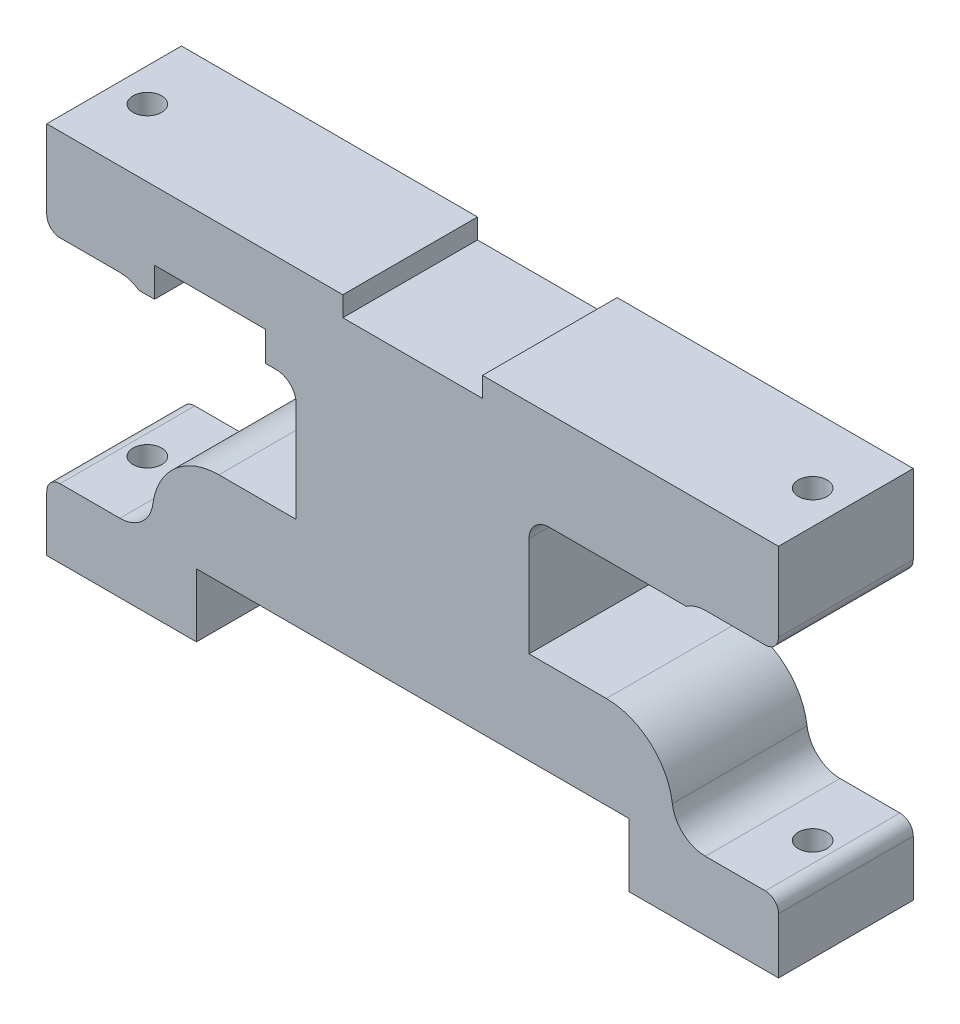
SolidWorks part; units mm, degrees
ref_plane "Front Plane" through (0, 0, 0) normal (0, 0, 1) x (1, 0, 0)
ref_plane "Top Plane" through (0, 0, 0) normal (0, 1, 0) x (1, 0, 0)
ref_plane "Right Plane" through (0, 0, 0) normal (1, 0, 0) x (0, 0, -1)
sketch "Sketch1" plane through (0, 0, 0) normal (0, 1, 0) x (1, 0, 0)
  line L0 (-50, 0) -> (-47.841, 0) construction
  line L21 (47.841, 0) -> (50, 0) construction
  line L22 (-50, 0) -> (-47.841, 0) construction
  line L38 (47.841, 0) -> (50, 0) construction
  line L40 (-55, 10.125) -> (55, 10.125)
  line L41 (-55, 10.125) -> (-55, -10.125)
  line L42 (-55, -10.125) -> (55, -10.125)
  line L43 (55, 10.125) -> (55, -10.125)
  line L44 (-55, 10.125) -> (55, -10.125) construction
  line L45 (-55, -10.125) -> (55, 10.125) construction
  circle A0 centre (-50, 0) radius 2.159
  circle A1 centre (50, 0) radius 2.159
  point P0 (0, 0)
  point P1 (0, 0)
  dimension "D4" = 4.318
  dimension "D5" = 4.318
  dimension "D6" = 5
  dimension "D2" = 20.25
  dimension "D3" = 110
  dimension "D1" = 100
extrude "Boss-Extrude1" add sketch "Sketch1" along normal blind 43.175
sketch "Sketch2" plane through (0, 0, 0) normal (1, 0, 0) x (0, 0, -1)
  line L0 (-10.125, 0) -> (10.125, 0) construction
  line L1 (-36.8851, 36) -> (38.0609, 36)
  line L2 (-36.8851, 36) -> (-36.8851, 4)
  line L3 (-36.8851, 4) -> (38.0609, 4)
  line L4 (38.0609, 36) -> (38.0609, 4)
  dimension "D1" = 32
  dimension "D2" = 4
extrude "Cut-Extrude3" cut sketch "Sketch2" along normal through all from offset 39 contours L4 L3 L2 L1
extrude "Cut-Extrude4" cut sketch "Sketch2<3>" against normal through all from offset 39 offset against normal yes
sketch "Sketch2<3>" plane through (0, 0, 0) normal (1, 0, 0) x (0, 0, -1) same geometry as "Sketch2"
fillet "Fillet1" radius 5 4 edges at (-39, 36, 0) (-39, 4, 0) (39, 4, 0) (39, 36, 0)
fillet "Fillet2" radius 2 4 edges at (55, 4, 0) (55, 36, 0) (-55, 36, 0) (-55, 4, 0)
sketch "Sketch10" plane through (0, 0, 0) normal (0, -1, 0) x (1, 0, 0)
  line L0 (55, -10.125) -> (-55, -10.125) construction
  line L1 (-32.5, 10.125) -> (32.5, 10.125)
  line L2 (-32.5, 10.125) -> (-32.5, -10.125)
  line L3 (-32.5, -10.125) -> (32.5, -10.125)
  line L4 (32.5, 10.125) -> (32.5, -10.125)
  line L5 (-32.5, 10.125) -> (32.5, -10.125) construction
  line L6 (-32.5, -10.125) -> (32.5, 10.125) construction
  point P0 (0, 0)
  dimension "D1" = 65
extrude "Cut-Extrude8" cut sketch "Sketch10" against normal blind 3.175
sketch "Sketch11" plane through (0, 0, 10.125) normal (0, 0, 1) x (1, 0, 0)
  line L0 (17.5, 17.0962) -> (47.5, 17.0962)
  line L1 (-46.8673, 35.0962) -> (-17.5, 35.0962)
  line L2 (-46.8673, 35.0962) -> (-46.8673, 17.0962)
  line L3 (-46.8673, 17.0962) -> (-17.5, 17.0962)
  line L4 (47.5, 35.0962) -> (47.5, 17.0962)
  line L6 (-17.5, 35.0962) -> (-17.5, 17.0962)
  line L8 (17.5, 35.0962) -> (17.5, 17.0962)
  line L11 (17.5, 35.0962) -> (47.5, 35.0962)
  arc A0 (-39, 31) -> (-44, 36) centre (-44, 31) ccw construction
  point P7 (0, 30.7484)
  dimension "D1" = 17.5
  dimension "D2" = 17.5
  dimension "D3" = 18
extrude "Cut-Extrude9" cut sketch "Sketch11" against normal through all
fillet "Fillet3" radius 10 2 edges at (39, 17.0962, 0) (-39, 17.0962, 0)
fillet "Fillet5" radius 3 2 edges at (17.5, 35.0962, 0) (-17.5, 35.0962, 0)
sketch "Sketch13" plane through (0, 43.175, 0) normal (0, 1, 0) x (1, 0, 0)
  line L1 (-55, 10.125) -> (55, 10.125)
  line L2 (-55, 10.125) -> (-55, -10.125)
  line L3 (-55, -10.125) -> (55, -10.125)
  line L4 (55, 10.125) -> (55, -10.125)
sketch "Sketch16" plane through (0, 0, 0) normal (0, -1, 0) x (1, 0, 0)
  line L1 (-55, 10.125) -> (-32.5, 10.125)
  line L2 (-55, 10.125) -> (-55, -10.125)
  line L3 (-55, -10.125) -> (-32.5, -10.125)
  line L4 (-32.5, 10.125) -> (-32.5, -10.125)
  line L5 (32.5, 10.125) -> (55, 10.125)
  line L6 (32.5, 10.125) -> (32.5, -10.125)
  line L7 (32.5, -10.125) -> (55, -10.125)
  line L8 (55, 10.125) -> (55, -10.125)
extrude "Boss-Extrude4" add sketch "Sketch16" along normal blind 6.35
extrude "Boss-Extrude5" add sketch "Sketch13" along normal blind 3.675
sketch "Sketch19" plane through (0, 46.85, 0) normal (0, 1, 0) x (1, 0, 0)
  line L0 (-55, -10.125) -> (55, -10.125) construction
  line L2 (-10.5, 10.125) -> (-10.5, -10.125)
  line L4 (10.5, 10.125) -> (10.5, -10.125)
  line L7 (10.5, 10.125) -> (55, 10.125)
  line L8 (-55, 10.125) -> (-10.5, 10.125)
  line L9 (-55, 10.125) -> (-55, -10.125)
  line L10 (-55, -10.125) -> (-10.5, -10.125)
  line L11 (55, 10.125) -> (55, -10.125)
  line L12 (10.5, -10.125) -> (55, -10.125)
  point P0 (0, 0)
  dimension "D1" = 21
  dimension "D2" = 10.5
extrude "Boss-Extrude6" add sketch "Sketch19" along normal blind 3
sketch "Sketch20" plane through (0, 4, 0) normal (0, 1, 0) x (1, 0, 0)
  circle A0 centre (-50, 0) radius 2.159
  circle A1 centre (50, 0) radius 2.159
extrude "Cut-Extrude10" cut sketch "Sketch20" along normal through all and the other way through all
sketch "Sketch21" plane through (0, 0, 10.125) normal (0, 0, 1) x (1, 0, 0)
  line L0 (-20.5, 35.0962) -> (-41.1327, 35.0962) construction
  line L1 (-38.8014, 35.0962) -> (-22.1168, 35.0962)
  line L2 (-38.8014, 35.0962) -> (-38.8014, 39.534)
  line L3 (-38.8014, 39.534) -> (-22.1168, 39.534)
  line L4 (-22.1168, 35.0962) -> (-22.1168, 39.534)
extrude "Cut-Extrude11" cut sketch "Sketch21" against normal through all
